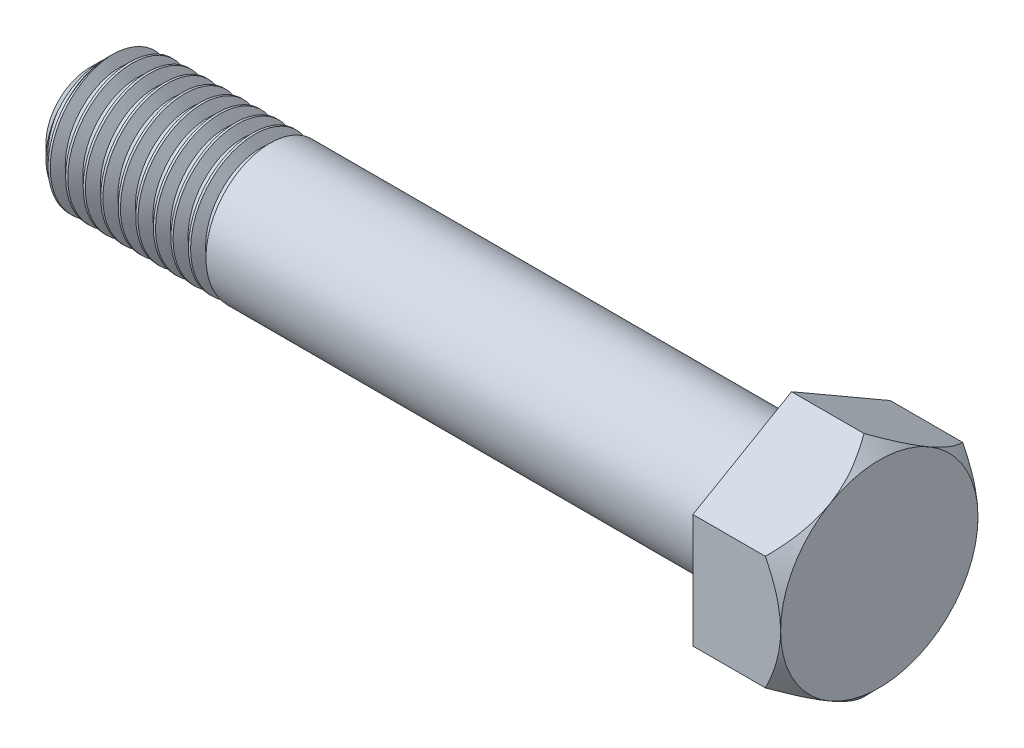
SolidWorks part; units mm, degrees
material "Plain Carbon Steel"
ref_plane "Front" through (0, 0, 0) normal (0, 0, 1) x (1, 0, 0)
ref_plane "Top" through (0, 0, 0) normal (0, 1, 0) x (1, 0, 0)
ref_plane "Right" through (0, 0, 0) normal (1, 0, 0) x (0, 0, -1)
sketch "Sketch1" plane through (0, 0, 0) normal (1, 0, 0) x (0, 0, -1)
  line L1 (14.2875, 8.2489) -> (0, 16.4978)
  line L2 (0, 16.4978) -> (-14.2875, 8.2489)
  line L3 (-14.2875, 8.2489) -> (-14.2875, -8.2489)
  line L4 (-14.2875, -8.2489) -> (0, -16.4978)
  line L5 (0, -16.4978) -> (14.2875, -8.2489)
  line L6 (14.2875, -8.2489) -> (14.2875, 8.2489)
  circle A0 centre (0, 0) radius 14.2875 construction
  circle A1 centre (0, 0) radius 9.525
  dimension "D2" = 19.05
  dimension "D1" = 28.575
extrude "Boss-Extrude1" add sketch "Sketch1" along normal blind 12.7 contours L1 L2 L3 L4 L5 L6
extrude "Boss-Extrude2" add sketch "Sketch1<3>" against normal blind 101.6 contours A1
sketch "Sketch1<3>" plane through (0, 0, 0) normal (1, 0, 0) x (0, 0, -1) same geometry as "Sketch1"
thread "Thread1" pitch 2.54 method cut profile "Thread Profile1" start angle 0, offset 0, length 25.4, pitch 2.54, diameter 19.05
ref_plane "Plane2" through (-101.6, 0, -9.525) normal (0, -1, 0) x (0, 0, -1)
sketch "Thread Profile1" plane through (-101.6, 0, -9.525) normal (0, -1, 0) x (0, 0, -1)
  line L0 (0, 0) -> (0, 2.54) construction
  line L11 (0, 0) -> (0, 2.2225)
  line L12 (0, 2.2225) -> (-1.3748, 1.4287)
  line L13 (-1.3748, 1.4287) -> (-1.3748, 0.7937)
  line L15 (-1.3748, 0.7937) -> (0, 0)
  line L17 (-1.3748, 1.1112) -> (0, 1.1112) construction
  point P2 (0, 0)
  dimension "Pitch" = 2.54
  dimension "Profile_Angle" = 60
  dimension "Profile_Land" = 0.635
  dimension "Profile_Height" = 1.3748
sketch "Sketch4" plane through (0, 0, 0) normal (0, 0, 1) x (1, 0, 0)
  line L0 (12.7, -16.4978) -> (12.7, 16.4978)
  line L1 (12.7, -16.4978) -> (12.7, 16.4978)
  line L2 (12.7, 16.4978) -> (0, 16.4978) construction
  line L3 (12.7, 16.4978) -> (0, 16.4978)
  line L4 (12.7, 14.2875) -> (10.4897, 16.4978)
  line L5 (12.7, 0) -> (27.2964, 0) construction
  point P5 (12.7, 0)
  dimension "D1" = 14.2875
  dimension "D2" = 45
revolve "Cut-Revolve1" cut sketch "Sketch4" angle 360 about L5 region at (11.9632, 15.761, 0)
fillet "Fillet1" radius 1.524 1 edges at (0, 0, -9.525)
sketch "Sketch12" plane through (0, 0, 0) normal (0, 1, 0) x (1, 0, 0)
  line L0 (-101.6, -6.35) -> (-98.425, -9.525)
  line L1 (-98.425, -9.525) -> (-101.6, -9.525)
  line L2 (-101.6, -9.525) -> (-101.6, -6.35)
  line L3 (-127.4965, 0) -> (-139.7468, 0)
  dimension "D1" = 3.175
revolve "Cut-Revolve3" cut sketch "Sketch12" angle 360 about L3 region at (-100.5417, 0, 8.4667)
equation "\"Length\"= 5in"
